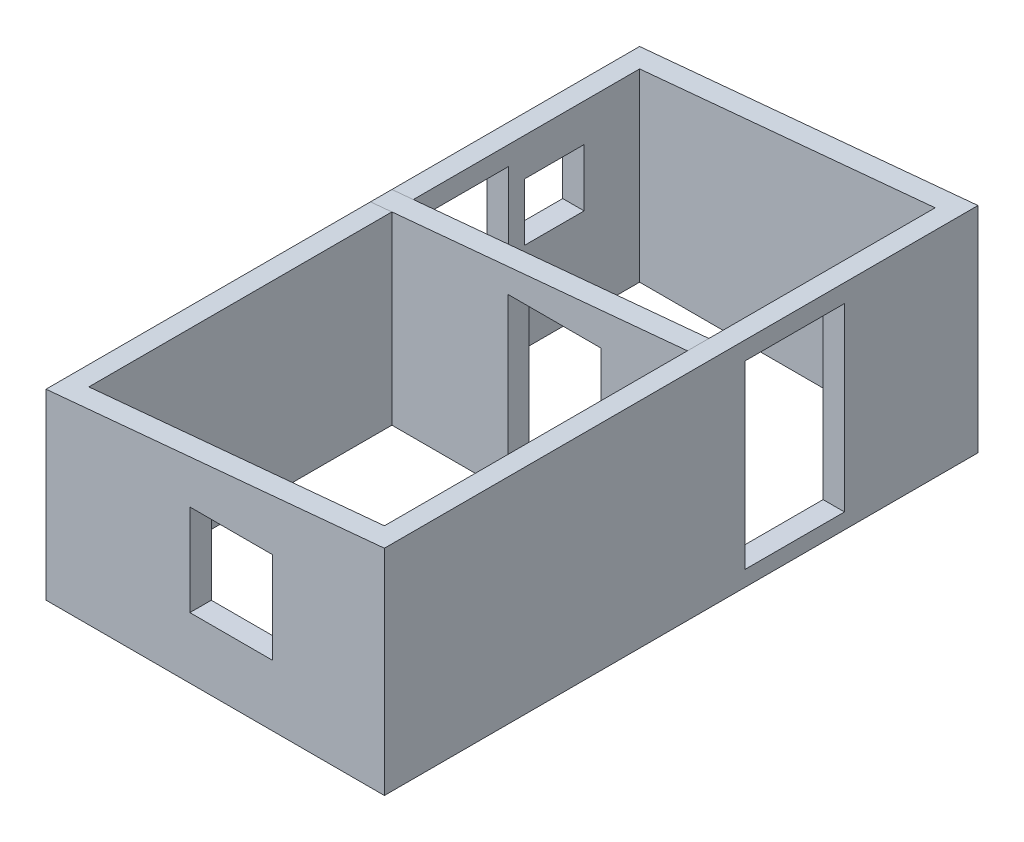
SolidWorks part; units mm, degrees
ref_plane "Спереди" through (0, 0, 0) normal (0, 0, 1) x (1, 0, 0)
ref_plane "Сверху" through (0, 0, 0) normal (0, 1, 0) x (1, 0, 0)
ref_plane "Справа" through (0, 0, 0) normal (1, 0, 0) x (0, 0, -1)
sketch "Эскиз1" plane through (0, 0, 0) normal (0, 1, 0) x (1, 0, 0)
  line L0 (0, 5543) -> (3160, 5543)
  line L1 (0, 5543) -> (0, 0)
  line L2 (0, 0) -> (3160, 0)
  line L3 (3160, 5543) -> (3160, 0)
  line L4 (0, 3029.9975) -> (3160, 3029.9975)
extrude "Вытянуть-Тонкостенный1" add sketch "Эскиз1" along normal blind 2000 thin thin type one direction reverse wall 200
sketch "Эскиз2" plane through (0, 0, 0) normal (0, 0, 1) x (1, 0, 0)
  line L0 (0, 2000) -> (3160, 2000)
  line L1 (3160, 2000) -> (0, 1706.1006)
  line L2 (0, 2000) -> (0, 0) construction
  line L3 (0, 1706.1006) -> (0, 2000)
extrude "Вырез-Вытянуть1" cut sketch "Эскиз2" against normal through all
sketch "Эскиз3" plane through (0, 0, 0) normal (-1, 0, 0) x (0, 0, 1)
  line L0 (-5543, 0) -> (0, 0) construction
  line L1 (-4825.1469, 1372.0739) -> (-4266.3924, 1372.0739)
  line L2 (-4825.1469, 1372.0739) -> (-4825.1469, 835.2313)
  line L3 (-4825.1469, 835.2313) -> (-4266.3924, 835.2313)
  line L4 (-4266.3924, 1372.0739) -> (-4266.3924, 835.2313)
  line L5 (-4118.4868, 1547.3694) -> (-3313.2229, 1547.3694)
  line L6 (-4118.4868, 1547.3694) -> (-4118.4868, 0)
  line L7 (-4118.4868, 0) -> (-3313.2229, 0)
  line L8 (-3313.2229, 1547.3694) -> (-3313.2229, 0)
extrude "Вырез-Вытянуть2" cut sketch "Эскиз3" against normal up to surface (200 mm away) up to face at (200, 862.3509, -2771.5)
sketch "Эскиз4" plane through (0, 0, 0) normal (0, 0, 1) x (1, 0, 0)
  line L1 (1343.6154, 1425.4) -> (2115.8531, 1425.4)
  line L2 (1343.6154, 1425.4) -> (1343.6154, 571.1547)
  line L3 (1343.6154, 571.1547) -> (2115.8531, 571.1547)
  line L4 (2115.8531, 1425.4) -> (2115.8531, 571.1547)
extrude "Вырез-Вытянуть3" cut sketch "Эскиз4" against normal up to surface (200 mm away) up to face at (1580, 926.5252, -200)
sketch "Эскиз5" plane through (0, 0, -3029.9975) normal (0, 0, 1) x (1, 0, 0)
  line L1 (1282.3926, 1599.7596) -> (2153.3572, 1599.7596)
  line L2 (1282.3926, 1599.7596) -> (1282.3926, 0)
  line L3 (1282.3926, 0) -> (2153.3572, 0)
  line L4 (2153.3572, 1599.7596) -> (2153.3572, 0)
extrude "Вырез-Вытянуть4" cut sketch "Эскиз5" against normal up to surface (200 mm away) up to face at (1580, 926.5252, -3229.9975)
sketch "Эскиз6" plane through (3160, 0, 0) normal (1, 0, 0) x (0, 0, -1)
  line L1 (3365.8902, 1830.6847) -> (4296.452, 1830.6847)
  line L2 (3365.8902, 1830.6847) -> (3365.8902, 144.955)
  line L3 (3365.8902, 144.955) -> (4296.452, 144.955)
  line L4 (4296.452, 1830.6847) -> (4296.452, 144.955)
extrude "Вырез-Вытянуть5" cut sketch "Эскиз6" against normal up to surface (200 mm away) up to face at (2960, 990.6994, -2771.5)
